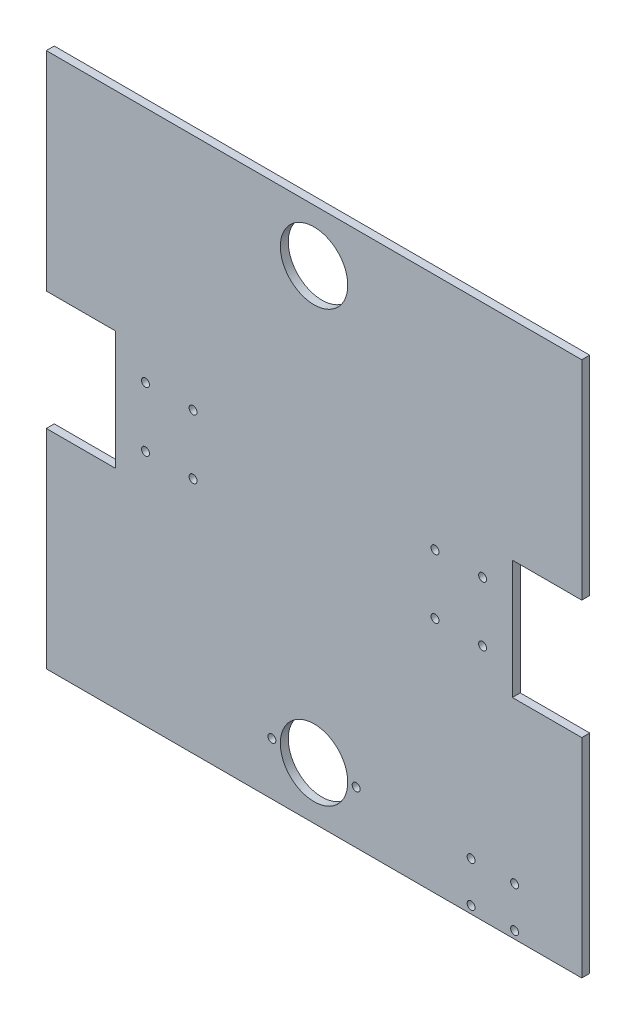
SolidWorks part; units mm, degrees
material "Alumina"
ref_plane "Front Plane" through (0, 0, 0) normal (0, 0, 1) x (1, 0, 0)
ref_plane "Top Plane" through (0, 0, 0) normal (0, 1, 0) x (1, 0, 0)
ref_plane "Right Plane" through (0, 0, 0) normal (1, 0, 0) x (0, 0, -1)
sketch "Sketch1" plane through (0, 0, 0) normal (0, 0, 1) x (1, 0, 0)
  line L1 (-135, 135) -> (135, 135)
  line L2 (-135, 135) -> (-135, -135)
  line L3 (-135, -135) -> (135, -135)
  line L4 (135, 135) -> (135, -135)
  line L5 (-135, 135) -> (135, -135) construction
  line L6 (-135, -135) -> (135, 135) construction
  point P0 (0, 0)
  dimension "D1" = 270
  dimension "D2" = 270
extrude "Boss-Extrude1" add sketch "Sketch1" along normal blind 4
sketch "Sketch2" plane through (0, 0, 4) normal (0, 0, 1) x (1, 0, 0)
  line L0 (-135, 135) -> (-135, -135) construction
  line L1 (-135, 30) -> (-100, 30)
  line L2 (-135, 30) -> (-135, -30)
  line L3 (-135, -30) -> (-100, -30)
  line L4 (-100, 30) -> (-100, -30)
  line L5 (-135, 30) -> (-100, -30) construction
  line L6 (-135, -30) -> (-100, 30) construction
  circle A0 centre (-85, 15) radius 2
  circle A1 centre (-61, 15) radius 2
  circle A2 centre (-61, -15) radius 2
  circle A3 centre (-85, -15) radius 2
  point P0 (-117.5, 0)
  dimension "D3" = 4
  dimension "D4" = 24
  dimension "D5" = 30
  dimension "D6" = 50
  dimension "D1" = 35
  dimension "D2" = 60
extrude "Cut-Extrude1" cut sketch "Sketch2" against normal through all
sketch "Sketch3" plane through (0, 0, 4) normal (0, 0, 1) x (1, 0, 0)
  line L1 (0, -108.5) -> (0, -88.5) construction
  line L2 (0, -108.5) -> (17.3205, -118.5) construction
  line L3 (0, -108.5) -> (-17.3205, -118.5) construction
  circle A3 centre (0, -108.5) radius 17
  point P1 (0, -47.1968)
  point P2 (0, -104.443)
  point P4 (0, -108.1352)
  point P7 (0, -108.5)
  dimension "D2" = 34
  dimension "D4" = 120
  dimension "D5" = 120
  dimension "D6" = 20
extrude "Cut-Extrude2" cut sketch "Sketch3" against normal through all
mirror "Mirror1" about plane through (0, 0, 0) normal (1, 0, 0) of "Cut-Extrude1"
mirror "Mirror2" about plane through (0, 0, 0) normal (0, 1, 0) of "Cut-Extrude2"
sketch "Sketch4" plane through (0, 0, 4) normal (0, 0, 1) x (1, 0, 0)
  circle A0 centre (21.25, -108.5) radius 2
  circle A1 centre (-21.25, -108.5) radius 2
  dimension "D1" = 4
extrude "Cut-Extrude3" cut sketch "Sketch4" against normal through all
sketch "Sketch5" plane through (0, 0, 4) normal (0, 0, 1) x (1, 0, 0)
  circle A0 centre (79.2065, -131.2348) radius 2
  circle A1 centre (79.2065, -110.7652) radius 2
  circle A2 centre (101.1382, -110.7652) radius 2
  circle A3 centre (101.1382, -131.2348) radius 2
  dimension "D1" = 4
extrude "Cut-Extrude4" cut sketch "Sketch5" against normal through all
